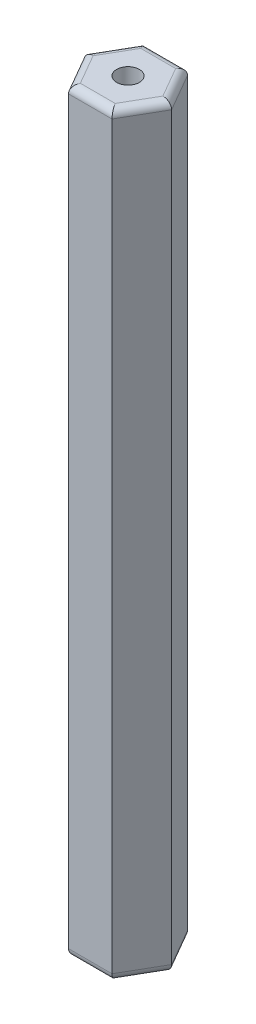
SolidWorks part; units mm, degrees
ref_plane "Plano frontal" through (0, 0, 0) normal (0, 0, 1) x (1, 0, 0)
ref_plane "Plano superior" through (0, 0, 0) normal (0, 1, 0) x (1, 0, 0)
ref_plane "Plano direito" through (0, 0, 0) normal (1, 0, 0) x (0, 0, -1)
ref_plane "Plano1" through (0, -30, 0) normal (0, -1, 0) x (1, 0, 0)
sketch "Esboço1" plane through (0, -30, 0) normal (0, -1, 0) x (1, 0, 0)
  line L0 (-1.4434, -2.5) -> (1.4434, -2.5)
  line L1 (1.4434, -2.5) -> (2.8868, 0)
  line L2 (2.8868, 0) -> (1.4434, 2.5)
  line L3 (1.4434, 2.5) -> (-1.4434, 2.5)
  line L4 (-1.4434, 2.5) -> (-2.8868, 0)
  line L5 (-2.8868, 0) -> (-1.4434, -2.5)
  line L6 (0, 2.5) -> (0, -2.5) construction
  circle A0 centre (0, 0) radius 2.8868 construction
  dimension "D1" = 5
extrude "Ressalto-extrusão1" add sketch "Esboço1" against normal blind 50
fillet "Filete1" radius 0.5 12 edges at (0, -30, 2.5) (2.1651, -30, 1.25) (-2.1651, -30, 1.25) (2.1651, -30, -1.25) (-2.1651, -30, -1.25) (0, -30, -2.5) (0, 20, 2.5) (2.1651, 20, 1.25) (-2.1651, 20, 1.25) (2.1651, 20, -1.25) (-2.1651, 20, -1.25) (0, 20, -2.5)
sketch "Esboço2" plane through (0, -30, 0) normal (0, -1, 0) x (1, 0, 0)
  circle A0 centre (0, 0) radius 0.7514
extrude "Corte-extrusão1" cut sketch "Esboço2" against normal through all
